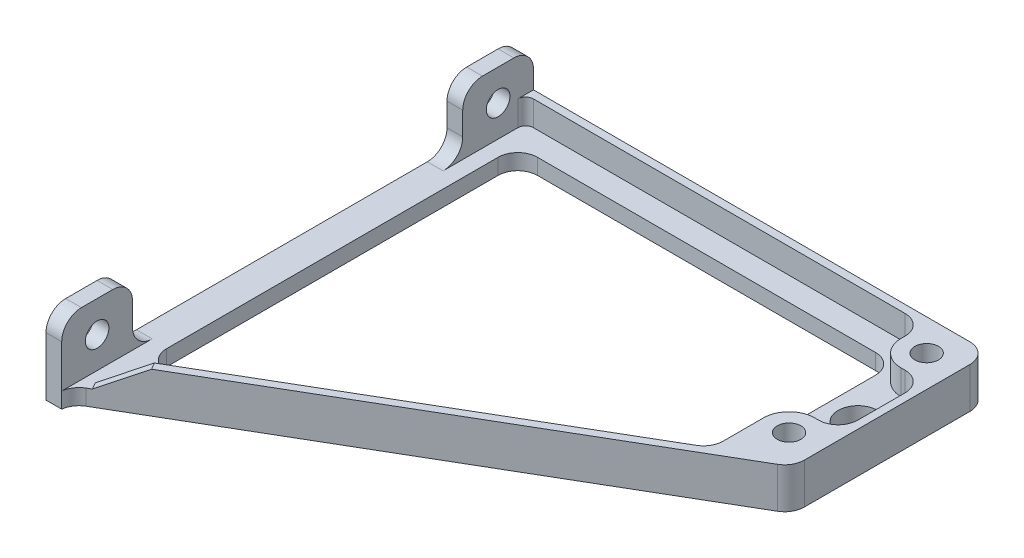
SolidWorks part; units mm, degrees
ref_plane "Front Plane" through (0, 0, 0) normal (0, 0, 1) x (1, 0, 0)
ref_plane "Top Plane" through (0, 0, 0) normal (0, 1, 0) x (1, 0, 0)
ref_plane "Right Plane" through (0, 0, 0) normal (1, 0, 0) x (0, 0, -1)
sketch "Sketch1" plane through (0, 0, 0) normal (0, 1, 0) x (1, 0, 0)
  line L0 (0, 0) -> (120, 0)
  line L1 (120, 0) -> (120, -50)
  line L2 (120, -50) -> (4, -117.6667)
  line L3 (0, -120) -> (0, 0)
  line L4 (110, 0) -> (110, -55.8333) construction
  line L5 (0, -120) -> (4, -120)
  line L6 (4, -120) -> (4, -117.6667)
  line L7 (4, -117.6667) -> (0, -120) construction
  dimension "D1" = 50
  dimension "D2" = 110
  dimension "D3" = 10
  dimension "D4" = 120
  dimension "D5" = 4
extrude "Boss-Extrude1" add sketch "Sketch1" along normal blind 4
sketch "Sketch2" plane through (0, 4, 0) normal (0, 1, 0) x (1, 0, 0)
  line L0 (112, -8) -> (112, -43) construction
  line L1 (104, -8) -> (104, -50.0717)
  line L2 (104, -8) -> (8, -8)
  line L3 (8, -8) -> (8, -106.0717)
  line L4 (8, -106.0717) -> (104, -50.0717)
  line L7 (0, 0) -> (0, -120)
  line L8 (0, -120) -> (4, -120)
  line L9 (4, -120) -> (4, -117.6667)
  line L10 (4, -117.6667) -> (120, -50)
  line L11 (120, -50) -> (120, 0)
  line L12 (120, 0) -> (0, 0)
  line L13 (0, 0) -> (0, -120)
  line L14 (0, -120) -> (4, -120)
  line L15 (4, -120) -> (4, -117.6667)
  line L16 (4, -117.6667) -> (120, -50)
  line L17 (120, -50) -> (120, 0)
  line L18 (120, 0) -> (0, 0)
  circle A0 centre (112, -8) radius 3
  circle A1 centre (112, -43) radius 3
  dimension "D4" = 6
  dimension "D1" = 35
  dimension "D2" = 112
  dimension "D3" = 8
  dimension "D6" = 8
  dimension "D7" = 8
  dimension "D8" = 8
  dimension "D5" = 0
extrude "Cut-Extrude3" cut sketch "Sketch2" against normal through all contours L1 L4 L3 L2 | A0 | A1
sketch "Sketch7" plane through (0, 4, 0) normal (0, 1, 0) x (1, 0, 0)
  line L0 (2.9923, -115.9391) -> (118, -48.8513)
  line L1 (118, -48.8513) -> (118, -2)
  line L2 (118, -2) -> (2.9923, -2)
  line L3 (2.9923, -115.9391) -> (4, -117.6667)
  line L4 (2, -118) -> (2, -118)
  line L5 (2.9923, -2) -> (2.9923, 0)
  line L6 (0, 0) -> (0, -120)
  line L7 (0, -120) -> (4, -120)
  line L8 (4, -120) -> (4, -117.6667)
  line L9 (4, -117.6667) -> (120, -50)
  line L10 (120, -50) -> (120, 0)
  line L11 (120, 0) -> (0, 0)
  line L12 (0, 0) -> (0, -120)
  line L13 (0, -120) -> (4, -120)
  line L14 (4, -120) -> (4, -117.6667)
  line L15 (4, -117.6667) -> (120, -50)
  line L16 (120, -50) -> (120, 0)
  line L17 (120, 0) -> (0, 0)
  line L18 (118, -2) -> (2, -2) construction
  line L20 (2, -2) -> (2, -118) construction
  line L21 (2, -118) -> (2, -116.5179) construction
  line L22 (2, -116.5179) -> (118, -48.8513) construction
  point P12 (0, 0)
  dimension "D1" = 0
  dimension "D2" = 2
extrude "Boss-Extrude3" add sketch "Sketch7" along normal blind 6.35
chamfer "Chamfer1" distance 15 angle 30 1 edges at (3.4961, 10.35, 116.8029)
sketch "Sketch8" plane through (0, 4, 0) normal (0, 1, 0) x (1, 0, 0)
  line L0 (112, -14.5) -> (118, -14.5)
  line L1 (118, -48.8513) -> (118, -2) construction
  line L2 (105.5, -8) -> (105.5, -2)
  line L3 (118, -2) -> (2.9923, -2) construction
  line L4 (105.5, -2) -> (118, -2)
  line L5 (118, -2) -> (118, -14.5)
  line L6 (112, -36.5) -> (118, -36.5)
  line L7 (105.5, -43) -> (105.5, -56.1429)
  line L8 (6.4486, -113.9229) -> (118, -48.8513) construction
  line L9 (118, -36.5) -> (118, -48.8513)
  line L10 (118, -48.8513) -> (105.5, -56.1429)
  circle A0 centre (112, -43) radius 3 construction
  circle A1 centre (112, -8) radius 3 construction
  circle A2 centre (112, -43) radius 3
  circle A3 centre (112, -8) radius 3
  arc A4 (105.5, -8) -> (112, -14.5) centre (112, -8) ccw
  arc A5 (112, -36.5) -> (105.5, -43) centre (112, -43) ccw
  dimension "D1" = 3.5
extrude "Boss-Extrude4" add sketch "Sketch8" along normal blind 6.35
sketch "Sketch9" plane through (0, 4, 0) normal (0, 1, 0) x (1, 0, 0)
  line L0 (4, -120) -> (4, -117.6667) construction
  line L1 (0, 0) -> (4, 0)
  line L2 (0, 0) -> (0, -18)
  line L3 (0, -18) -> (4, -18)
  line L4 (4, 0) -> (4, -18)
  line L5 (0, -120) -> (4, -120)
  line L6 (0, -120) -> (0, -102)
  line L7 (0, -102) -> (4, -102)
  line L8 (4, -120) -> (4, -102)
  dimension "D1" = 18
extrude "Boss-Extrude5" add sketch "Sketch9" along normal blind 15.875
sketch "Sketch10" plane through (4, 0, 0) normal (1, 0, 0) x (0, 0, -1)
  line L1 (-120, 19.875) -> (-102, 4) construction
  line L2 (-18, 4) -> (0, 19.875) construction
  circle A0 centre (-9, 11.9375) radius 3
  circle A1 centre (-111, 11.9375) radius 3
  point P0 (0, 0)
  dimension "D1" = 6
extrude "Cut-Extrude4" cut sketch "Sketch10" against normal blind 110.875
fillet "Fillet3" radius 5 17 edges at (105.5, 7.175, 56.1429) (118, 7.175, 36.5) (118, 7.175, 14.5) (105.5, 7.175, 2) (120, 5.175, 0) (120, 5.175, 50) (4, 2, 117.6667) (8, 2, 106.0717) (104, 2, 50.0717) (104, 2, 8) (8, 2, 8) (2, 19.875, 120) (2, 4, 102) (2, 19.875, 102) (2, 19.875, 0) (2, 19.875, 18) (2, 4, 18)
sketch "Sketch11" plane through (0, 4, 0) normal (0, 1, 0) x (1, 0, 0)
  line L0 (112, -8) -> (112, -43) construction
  circle A0 centre (112, -25.5) radius 5
  dimension "D1" = 10
extrude "Cut-Extrude5" cut sketch "Sketch11" against normal blind 15.875
fillet "Fillet4" radius 2 1 edges at (4, 7.175, 2)
